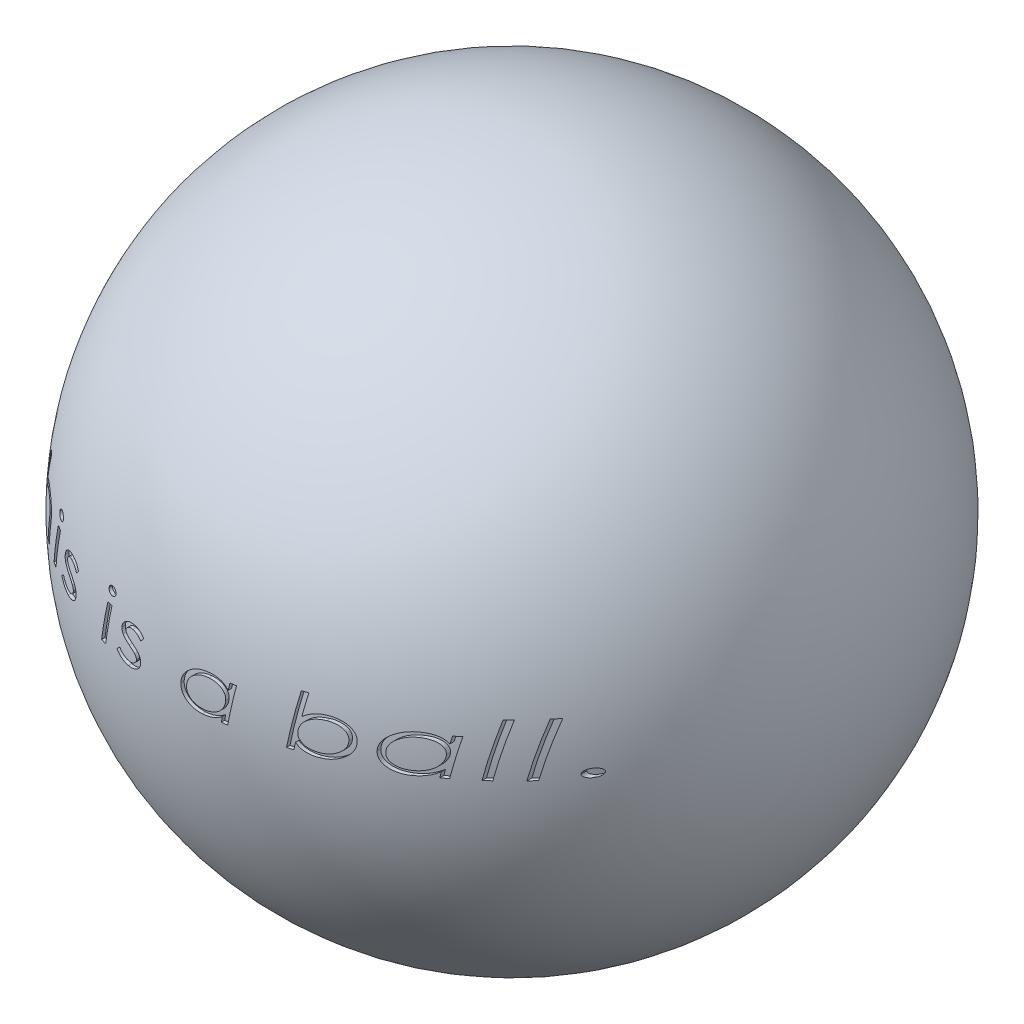
SolidWorks part; units mm, degrees
ref_plane "Front Plane" through (0, 0, 0) normal (0, 0, 1) x (1, 0, 0)
ref_plane "Top Plane" through (0, 0, 0) normal (0, 1, 0) x (1, 0, 0)
ref_plane "Right Plane" through (0, 0, 0) normal (1, 0, 0) x (0, 0, -1)
sketch "Sketch1" plane through (0, 0, 0) normal (0, 0, 1) x (1, 0, 0)
  line L0 (0, 0) -> (100, 0)
  arc A0 (0, 0) -> (100, 0) centre (50, 0) cw
  dimension "D2" = 50
  dimension "D1" = 100
revolve "Revolve1" add sketch "Sketch1" angle 360 about L0
ref_plane "Plane1" through (0, 0, 50) normal (0, 0, 1) x (1, 0, 0)
sketch "Sketch2" plane through (0, 0, 50) normal (0, 0, 1) x (1, 0, 0)
  line L0 (0, 0) -> (100, 0) construction
  text T0 "This is a ball." font "Century Gothic" height in points 28
  dimension "D1" = 100
extrude "Cut-Extrude2" cut sketch "Sketch2" against normal blind 40
sketch "Sketch3" plane through (0, 0, 0) normal (0, 0, 1) x (1, 0, 0)
  line L0 (0.5, 0) -> (99.5, 0)
  arc A0 (99.5, 0) -> (0.5, 0) centre (50, 0) ccw
  dimension "D1" = 99
  dimension "D2" = 50
revolve "Revolve2" add sketch "Sketch3" angle 360 about L0
